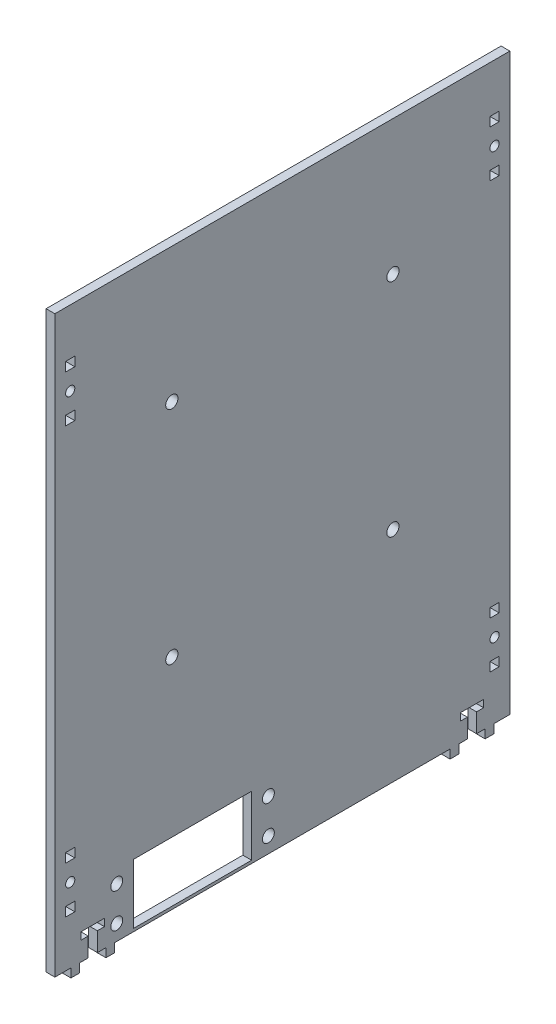
SolidWorks part; units mm, degrees
ref_plane "Front Plane" through (0, 0, 0) normal (0, 0, 1) x (1, 0, 0)
ref_plane "Top Plane" through (0, 0, 0) normal (0, 1, 0) x (1, 0, 0)
ref_plane "Right Plane" through (0, 0, 0) normal (1, 0, 0) x (0, 0, -1)
sketch "Sketch1" plane through (0, 0, 0) normal (1, 0, 0) x (0, 0, -1)
  line L0 (11.425, 0) -> (8.5, 0)
  line L1 (135.5, -3) -> (135.5, 0)
  line L2 (67.45, 21.5) -> (26.95, 21.5)
  line L3 (26.95, 21.5) -> (26.95, 1)
  line L4 (67.45, 21.5) -> (67.45, 1)
  line L5 (26.95, 1) -> (67.45, 1)
  line L6 (8.5, 0) -> (8.5, -3)
  line L7 (8.5, -3) -> (5.5, -3)
  line L8 (0, 0) -> (0, 197)
  line L9 (5.5, -3) -> (5.5, 0)
  line L10 (11.425, 0) -> (11.425, 6.5)
  line L11 (11.425, 6.5) -> (9, 6.5)
  line L12 (9, 6.5) -> (9, 9)
  line L13 (9, 9) -> (17, 9)
  line L14 (17, 9) -> (17, 6.5)
  line L15 (17, 6.5) -> (14.575, 6.5)
  line L16 (14.575, 6.5) -> (14.575, 0)
  line L17 (-1000, 98.5) -> (49000, 98.5) construction
  line L18 (3.675, 16) -> (6.825, 16)
  line L19 (3.675, 16) -> (3.675, 19.15)
  line L20 (3.675, 19.15) -> (6.825, 19.15)
  line L21 (6.825, 16) -> (6.825, 19.15)
  line L22 (3.675, 16) -> (6.825, 19.15) construction
  line L23 (3.675, 19.15) -> (6.825, 16) construction
  line L24 (3.675, 32) -> (6.825, 32)
  line L25 (3.675, 32) -> (3.675, 35.15)
  line L26 (3.675, 35.15) -> (6.825, 35.15)
  line L27 (6.825, 32) -> (6.825, 35.15)
  line L28 (3.675, 32) -> (6.825, 35.15) construction
  line L29 (3.675, 35.15) -> (6.825, 32) construction
  line L30 (14.575, 0) -> (17.5, 0)
  line L31 (78, -1000) -> (78, 49000) construction
  line L32 (3.675, 161.85) -> (6.825, 165) construction
  line L33 (3.675, 165) -> (6.825, 161.85) construction
  line L34 (3.675, 177.85) -> (6.825, 181) construction
  line L35 (3.675, 181) -> (6.825, 177.85) construction
  line L36 (0, 197) -> (156, 197)
  line L37 (6.825, 165) -> (6.825, 161.85)
  line L38 (3.675, 161.85) -> (6.825, 161.85)
  line L39 (3.675, 165) -> (3.675, 161.85)
  line L40 (3.675, 165) -> (6.825, 165)
  line L41 (6.825, 181) -> (6.825, 177.85)
  line L42 (3.675, 177.85) -> (6.825, 177.85)
  line L43 (3.675, 181) -> (3.675, 177.85)
  line L44 (3.675, 181) -> (6.825, 181)
  line L45 (5.5, 0) -> (0, 0)
  line L46 (17.5, 0) -> (17.5, -3)
  line L47 (17.5, -3) -> (20.5, -3)
  line L48 (20.5, -3) -> (20.5, 0)
  line L49 (20.5, 0) -> (135.5, 0)
  line L50 (138.5, -3) -> (135.5, -3)
  line L51 (138.5, 0) -> (138.5, -3)
  line L52 (141.425, 0) -> (138.5, 0)
  line L53 (144.575, 0) -> (147.5, 0)
  line L54 (150.5, 0) -> (156, 0)
  line L55 (150.5, -3) -> (150.5, 0)
  line L56 (147.5, -3) -> (150.5, -3)
  line L57 (147.5, 0) -> (147.5, -3)
  line L58 (37, 71.9) -> (37, 153.9) construction
  line L59 (37, 153.9) -> (119, 153.9) construction
  line L60 (119, 153.9) -> (119, 71.9) construction
  line L61 (152.325, 181) -> (149.175, 177.85) construction
  line L62 (152.325, 177.85) -> (149.175, 181) construction
  line L63 (152.325, 165) -> (149.175, 161.85) construction
  line L64 (152.325, 161.85) -> (149.175, 165) construction
  line L65 (152.325, 35.15) -> (149.175, 32) construction
  line L66 (152.325, 32) -> (149.175, 35.15) construction
  line L67 (152.325, 19.15) -> (149.175, 16) construction
  line L68 (152.325, 16) -> (149.175, 19.15) construction
  line L69 (119, 71.9) -> (37, 71.9) construction
  line L85 (152.325, 181) -> (149.175, 181)
  line L86 (152.325, 181) -> (152.325, 177.85)
  line L87 (152.325, 177.85) -> (149.175, 177.85)
  line L88 (149.175, 181) -> (149.175, 177.85)
  line L89 (152.325, 165) -> (149.175, 165)
  line L90 (152.325, 165) -> (152.325, 161.85)
  line L91 (152.325, 161.85) -> (149.175, 161.85)
  line L92 (149.175, 165) -> (149.175, 161.85)
  line L93 (149.175, 32) -> (149.175, 35.15)
  line L94 (152.325, 35.15) -> (149.175, 35.15)
  line L95 (152.325, 32) -> (152.325, 35.15)
  line L96 (152.325, 32) -> (149.175, 32)
  line L97 (149.175, 16) -> (149.175, 19.15)
  line L98 (152.325, 19.15) -> (149.175, 19.15)
  line L99 (152.325, 16) -> (152.325, 19.15)
  line L100 (152.325, 16) -> (149.175, 16)
  line L101 (141.425, 6.5) -> (141.425, 0)
  line L102 (139, 6.5) -> (141.425, 6.5)
  line L103 (139, 9) -> (139, 6.5)
  line L104 (147, 9) -> (139, 9)
  line L105 (147, 6.5) -> (147, 9)
  line L106 (144.575, 6.5) -> (147, 6.5)
  line L107 (144.575, 0) -> (144.575, 6.5)
  line L109 (156, 0) -> (156, 197)
  circle A0 centre (5.25, 25.575) radius 1.575
  circle A1 centre (5.25, 171.425) radius 1.575
  circle A2 centre (150.75, 171.425) radius 1.575
  circle A3 centre (150.75, 25.575) radius 1.575
  circle A4 centre (73.2, 5.35) radius 2.05
  circle A5 centre (73.2, 17.15) radius 2.05
  circle A6 centre (21.2, 5.35) radius 2.05
  circle A7 centre (21.2, 17.15) radius 2.05
  circle A8 centre (40.1, 75) radius 2.1
  circle A9 centre (40.1, 150.8) radius 2.1
  circle A10 centre (115.9, 75) radius 2.1
  circle A11 centre (115.9, 150.8) radius 2.1
  point P3 (13, 9)
  point P4 (143, 9)
  point P16 (5.25, 17.575)
  point P29 (5.25, 33.575)
  point P58 (0, 98.5)
  point P65 (5.25, 163.425)
  point P66 (5.25, 179.425)
  point P88 (78, 0)
  point P98 (78, 153.9)
  point P102 (0, 0)
  point P104 (78, 197)
  point P105 (78, 0)
  point P112 (0, 0)
  point P114 (0, 0)
  point P121 (150.75, 179.425)
  point P122 (150.75, 163.425)
  point P123 (156, 98.5)
  point P124 (150.75, 33.575)
  point P125 (150.75, 17.575)
  dimension "D19" = 3.15
  dimension "D23" = 20.5
  dimension "D24" = 4.1
  dimension "D25" = 4.1
  dimension "D30" = 4.1
  dimension "D31" = 4.1
  dimension "D44" = 4.2
  dimension "D50" = 4.2
  dimension "D3" = 130
  dimension "D4" = 156
  dimension "D5" = 5.25
  dimension "D6" = 4.5
  dimension "D7" = 4.5
  dimension "D8" = 2.5
  dimension "D9" = 98.5
  dimension "D10" = 2.5
  dimension "D11" = 8
  dimension "D12" = 8
  dimension "D13" = 8
  dimension "D14" = 3.15
  dimension "D15" = 2.425
  dimension "D16" = 3.15
  dimension "D17" = 3.15
  dimension "D18" = 5.75
  dimension "D20" = 5.75
  dimension "D21" = 3.15
  dimension "D22" = 3.15
  dimension "D26" = 4.35
  dimension "D27" = 4.35
  dimension "D28" = 3
  dimension "D29" = 5.75
  dimension "D32" = 5.75
  dimension "D33" = 4.35
  dimension "D34" = 4.35
  dimension "D35" = 9.95
  dimension "D36" = 40.5
  dimension "D37" = 11.8
  dimension "D38" = 3
  dimension "D39" = 3
  dimension "D40" = 3
  dimension "D41" = 9
  dimension "D42" = 17.575
  dimension "D43" = 1
  dimension "D45" = 75
  dimension "D46" = 82
  dimension "D47" = 82
  dimension "D48" = 3.1
  dimension "D49" = 3.1
  dimension "D51" = 3.1
extrude "Boss-Extrude2" add sketch "Sketch1" along normal blind 1.5 and the other way blind 1.5
